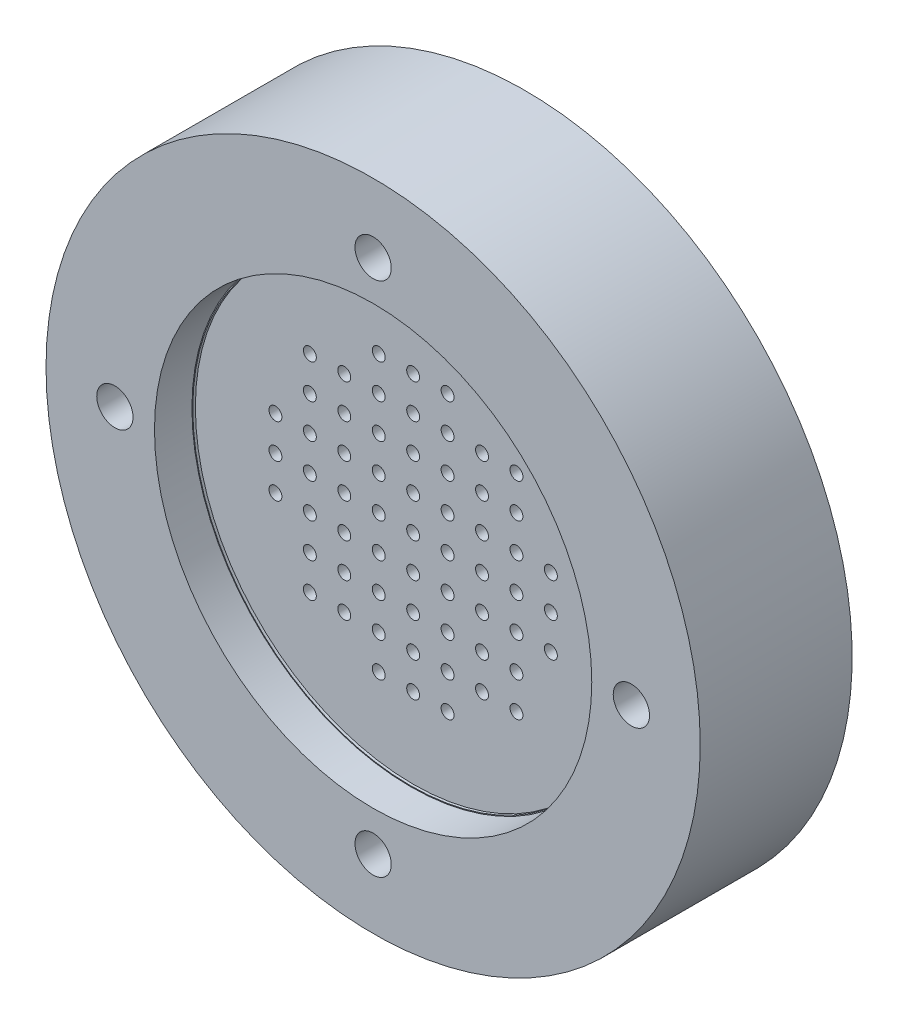
SolidWorks part; units mm, degrees
ref_plane "Plan de face" through (0, 0, 0) normal (0, 0, 1) x (1, 0, 0)
ref_plane "Plan de dessus" through (0, 0, 0) normal (0, 1, 0) x (1, 0, 0)
ref_plane "Plan de droite" through (0, 0, 0) normal (1, 0, 0) x (0, 0, -1)
sketch "Sketch1" plane through (0, 0, 0) normal (0, 0, 1) x (1, 0, 0)
  circle A0 centre (0, 0) radius 38
extrude "Boss-Extrude1" add sketch "Sketch1" along normal blind 5
sketch "Sketch2" plane through (0, 0, 5) normal (0, 0, 1) x (1, 0, 0)
  circle A0 centre (0, 0) radius 0.75
extrude "Cut-Extrude1" cut sketch "Sketch2" against normal through all
pattern_linear "LPattern1" count 5 spacing 4 along (0, 1, 0) count 5 spacing 4 along (1, 0, 0) skipping (2, 4), (3, 4), (4, 2), (4, 3), (4, 4) of "Cut-Extrude1"
mirror "Mirror1" about plane through (0, 0, 0) normal (1, 0, 0) of "LPattern1" second plane through (0, 0, 0) second plane normal (0, 1, 0)
sketch "Sketch16" plane through (0, 0, 5) normal (0, 0, 1) x (1, 0, 0)
  circle A0 centre (0, 0) radius 25.4
  circle A1 centre (0, 0) radius 38
extrude "Boss-Extrude2" add sketch "Sketch16" along normal blind 4.65
sketch "Sketch17" plane through (0, 0, 0) normal (0, 0, -1) x (-1, 0, 0)
  circle A0 centre (0, 0) radius 33
  circle A1 centre (0, 0) radius 38
extrude "Boss-Extrude3" add sketch "Sketch17" along normal blind 8
sketch "Sketch34" plane through (0, 0, 0) normal (0, 0, -1) x (-1, 0, 0)
  line L0 (0, -38) -> (0, -30)
  circle A0 centre (0, 0) radius 38 construction
hole_wizard "Hole for #4 300® SC Nuts (SP)3" positions "Sketch35" profile "Sketch36" hole size "#4-40" standard "PEM® Inch" end condition through all
sketch "Sketch35" plane through (0, 0, 0) normal (0, 0, -1) x (-1, 0, 0)
  point P0 (0, -30)
sketch "Sketch36" plane through (0, -30, 0) normal (1, 0, 0) x (0, 1, 0)
  line L0 (0, 0) -> (0, 9.65)
  line L1 (0, 9.65) -> (2.1082, 9.65)
  line L2 (2.1082, 9.65) -> (2.1082, 0)
  line L5 (2.1082, 0) -> (0, 0)
  line L11 (0, -6.35) -> (0, 107.95) construction
  dimension "Thru Hole Dia." = 4.2164
  dimension "Thru Hole Depth" = 9.65
pattern_circular "CirPattern1" count 4 over 360 about axis through (0, 0, 0) along (0, 0, 1) of "Hole for #4 300® SC Nuts (SP)3"
sketch "Sketch39" plane through (0, 0, -8) normal (0, 0, -1) x (-1, 0, 0)
  line L0 (0, -38) -> (0, -33)
  circle A0 centre (0, 0) radius 38 construction
  circle A1 centre (0, 0) radius 33 construction
hole_wizard "Hole for #4 300® SC Nuts (SP)4" positions "Sketch40" profile "Sketch41" hole size "#4-40" standard "PEM® Inch"
sketch "Sketch40" plane through (0, 0, -8) normal (0, 0, -1) x (-1, 0, 0)
  line L0 (0, -38) -> (0, -33) construction
  point P0 (0, -35.5)
sketch "Sketch41" plane through (0, -35.5, -8) normal (1, 0, 0) x (0, 1, 0)
  line L0 (0, 0) -> (0, 6.2667)
  line L1 (0, 6.2667) -> (2.1082, 5)
  line L2 (2.1082, 5) -> (2.1082, 0)
  line L5 (2.1082, 0) -> (0, 0)
  line L10 (0, 6.2667) -> (-2.1082, 5) construction
  line L11 (0, -6.35) -> (0, 107.95) construction
  dimension "Hole Dia." = 4.2164
  dimension "Hole Depth" = 5
  dimension "Drill Angle" = 118
pattern_circular "CirPattern2" count 3 over 360 about axis through (0, 0, 0) along (0, 0, 1) of "Hole for #4 300® SC Nuts (SP)4"
sketch "Sketch43" plane through (0, 0, 5) normal (0, 0, 1) x (1, 0, 0)
  circle A0 centre (0, 0) radius 25.3
  circle A1 centre (0, 0) radius 26.3
extrude "Boss-Extrude4" add sketch "Sketch43" along normal blind 0.3
